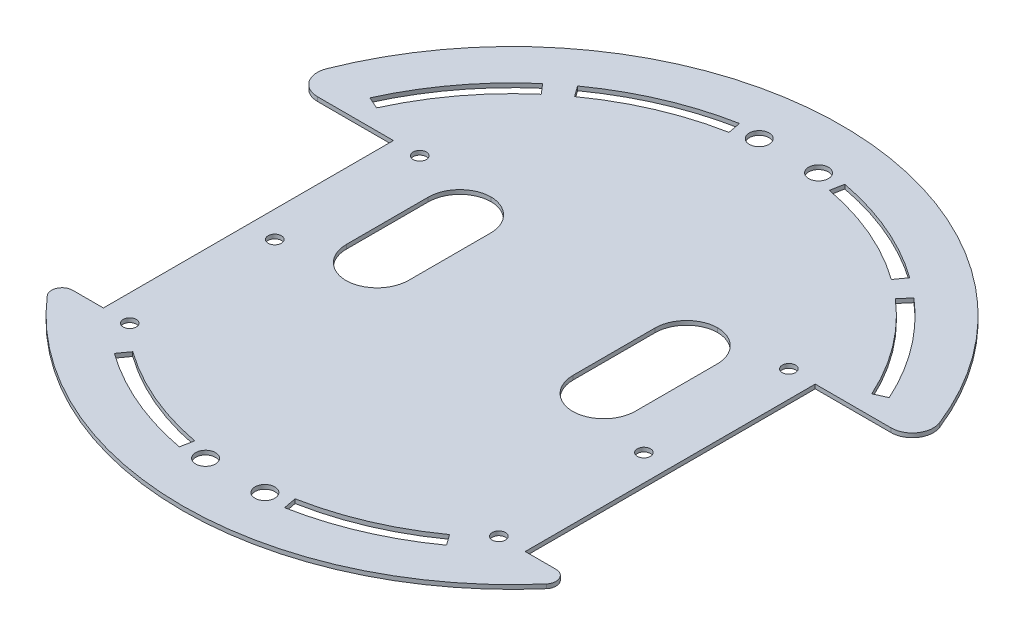
SolidWorks part; units mm, degrees
ref_plane "Front Plane" through (0, 0, 0) normal (0, 0, 1) x (1, 0, 0)
ref_plane "Top Plane" through (0, 0, 0) normal (0, 1, 0) x (1, 0, 0)
ref_plane "Right Plane" through (0, 0, 0) normal (1, 0, 0) x (0, 0, -1)
sketch "Sketch1" plane through (0, 0, 0) normal (0, 1, 0) x (1, 0, 0)
  line L0 (0, 0) -> (0, -79.375)
  line L1 (7.1438, -66.675) -> (-7.1437, -66.675)
  line L2 (50.8, 22.225) -> (76.2, 22.225)
  line L3 (-63.5, -47.625) -> (-50.8, -47.625)
  line L4 (-50.8, -47.625) -> (-50.8, 22.225)
  line L5 (63.5, -47.625) -> (50.8, -47.625)
  line L6 (50.8, -47.625) -> (50.8, 22.225)
  line L7 (-50.8, 22.225) -> (-76.2, 22.225)
  line L8 (0, 0) -> (-27.2811, 0)
  circle A0 centre (0, 0) radius 79.375
  circle A1 centre (-7.1437, -66.675) radius 1.5875
  circle A2 centre (7.1438, -66.675) radius 1.5875
  circle A3 centre (7.1438, 66.675) radius 1.5875
  circle A4 centre (-7.1437, 66.675) radius 1.5875
  point P7 (0, -66.675)
  dimension "D1" = 7.1437
  dimension "D3" = 50.8
  dimension "D6" = 3.175
  dimension "D2" = 12.7
  dimension "D4" = 69.85
  dimension "D5" = 47.625
extrude "Boss-Extrude5" add sketch "Sketch1" along normal blind 1.5875 contours A2 A0 L5 L6 L2 L7 L4 L3 A1 A3 region at (0, 0, -2.0947)
fillet "Fillet2" radius 2.54 1 edges at (-63.5, 0.7937, 47.625)
fillet "Fillet3" radius 2.54 1 edges at (63.5, 0.7937, 47.625)
fillet "Fillet4" radius 5.08 2 edges at (-76.2, 0.7937, -22.225) (76.2, 0.7937, -22.225)
sketch "Sketch2" plane through (0, 1.5875, 0) normal (0, 1, 0) x (1, 0, 0)
  line L0 (0, 0) -> (0, 79.375)
  line L1 (0, 0) -> (-67.0566, 0)
  line L2 (0, 0) -> (-61.0886, 27.6545)
  line L3 (0, 0) -> (-43.6778, 50.8806)
  line L4 (0, 0) -> (-63.2664, 22.225)
  line L5 (-50.8, 22.225) -> (-69.0955, 22.225) construction
  line L6 (0, 0) -> (0, 2.6153)
  line L7 (0, 0) -> (-39.0771, 54.4938)
  line L8 (0, 0) -> (-12.3858, 65.9028)
  line L9 (-62.5348, 28.3092) -> (-59.6424, 26.9998)
  line L10 (-43.6778, 50.8806) -> (-44.7118, 52.0852)
  line L11 (-43.6778, 50.8806) -> (-42.6438, 49.6761)
  line L12 (-39.0771, 54.4938) -> (-40.0022, 55.7839)
  line L13 (-39.0771, 54.4938) -> (-38.152, 53.2037)
  line L14 (-43.6778, 50.8806) -> (-42.6438, 49.6761)
  line L15 (-12.3858, 65.9028) -> (-12.0926, 64.3426)
  line L16 (-12.3858, 65.9028) -> (-12.679, 67.463)
  line L17 (61.5813, 22.225) -> (64.9466, 22.225)
  line L18 (50.8, 22.225) -> (69.0955, 22.225) construction
  line L19 (12.3858, 65.9028) -> (12.679, 67.463)
  line L20 (12.3858, 65.9028) -> (12.0926, 64.3426)
  line L21 (39.0771, 54.4938) -> (38.152, 53.2037)
  line L22 (43.6778, 50.8806) -> (42.6438, 49.6761)
  line L23 (39.0771, 54.4938) -> (40.0022, 55.7839)
  line L24 (43.6778, 50.8806) -> (42.6438, 49.6761)
  line L25 (43.6778, 50.8806) -> (44.7118, 52.0852)
  line L26 (62.5348, 28.3092) -> (59.6424, 26.9998)
  line L27 (-50.8, -41.2985) -> (-50.8, -43.7716)
  line L28 (-50.8, -47.625) -> (-50.8, 22.225) construction
  line L29 (50.8, -41.2985) -> (50.8, -46.1668)
  line L30 (50.8, -47.625) -> (50.8, 22.225) construction
  line L31 (39.0771, -54.4938) -> (40.0022, -55.7839)
  line L32 (39.0771, -54.4938) -> (38.152, -53.2037)
  line L33 (12.3858, -65.9028) -> (12.0926, -64.3426)
  line L34 (12.3858, -65.9028) -> (12.679, -67.463)
  line L35 (-12.3858, -65.9028) -> (-12.679, -67.463)
  line L36 (-12.3858, -65.9028) -> (-12.0926, -64.3426)
  line L37 (-39.0771, -54.4938) -> (-38.152, -53.2037)
  line L38 (-39.0771, -54.4938) -> (-40.0022, -55.7839)
  arc A0 (-63.2664, 22.225) -> (-50.8, -43.7716) centre (0, 0) ccw
  arc A1 (73.8199, 29.172) -> (-73.8199, 29.172) centre (0, 0) ccw construction
  circle A2 centre (-7.1437, 66.675) radius 2.3813
  circle A3 centre (7.1437, 66.675) radius 2.3813
  circle A4 centre (7.1437, -66.675) radius 2.3813
  circle A5 centre (-7.1437, -66.675) radius 2.3813
  arc A6 (12.679, -67.463) -> (40.0022, -55.7839) centre (0, 0) ccw
  arc A7 (-61.7686, 21.6988) -> (-50.8, -41.2985) centre (0, 0) ccw
  arc A8 (-44.7118, 52.0852) -> (-62.5348, 28.3092) centre (0, 0) ccw
  arc A9 (-42.6438, 49.6761) -> (-59.6424, 26.9998) centre (0, 0) ccw
  arc A10 (12.0926, 64.3426) -> (38.152, 53.2037) centre (0, 0) cw
  arc A11 (12.679, 67.463) -> (40.0022, 55.7839) centre (0, 0) cw
  arc A12 (42.6438, 49.6761) -> (59.6424, 26.9998) centre (0, 0) cw
  arc A13 (-12.679, 67.463) -> (-40.0022, 55.7839) centre (0, 0) ccw
  arc A14 (44.7118, 52.0852) -> (62.5348, 28.3092) centre (0, 0) cw
  arc A15 (-12.0926, 64.3426) -> (-38.152, 53.2037) centre (0, 0) ccw
  arc A16 (12.0926, -64.3426) -> (38.152, -53.2037) centre (0, 0) ccw
  arc A17 (-12.0926, -64.3426) -> (-38.152, -53.2037) centre (0, 0) cw
  arc A18 (50.8, -46.1668) -> (64.9466, 22.225) centre (0, 0) ccw
  arc A19 (50.8, -43.7716) -> (63.2664, 22.225) centre (0, 0) ccw
  arc A20 (50.8, -41.2985) -> (61.5813, 22.225) centre (0, 0) ccw
  arc A21 (-12.679, -67.463) -> (-40.0022, -55.7839) centre (0, 0) cw
  circle M13 centre (-7.1437, -66.675) radius 1.5875
  circle M14 centre (7.1438, -66.675) radius 1.5875
  circle M15 centre (7.1438, 66.675) radius 1.5875
  circle M16 centre (-7.1437, 66.675) radius 1.5875
  dimension "D2" = 4.7625
  dimension "D7" = 1.5875
  dimension "D8" = 3.175
  dimension "D1" = 5
  dimension "D3" = 25
  dimension "D4" = 5
  dimension "D5" = 25
extrude "Cut-Extrude1" cut sketch "Sketch2" against normal blind 2.54 contours A9 L3 L10 A8 L9 L2 | A15 L8 L16 A13 L12 L7 | A2 M16 | A3 M15 | A11 L19 L20 A10 L21 L23 | A14 L25 L22 A12 L26 | A21 L35 L36 A17 L37 L38 | A5 M13 | A4 M14 | A16 L33 L34 A6 L31 L32 region at (-53.2404, 1.5875, -39.9101) region at (-26.1525, 1.5875, -61.1833) region at (26.1525, 1.5875, -61.1833) region at (53.2404, 1.5875, -39.9101) region at (26.1525, 1.5875, 61.1833) region at (-26.1525, 1.5875, 61.1833) region at (-9.4576, 1.5875, -66.675) region at (4.8299, 1.5875, -66.675) region at (4.8299, 1.5875, 66.675) region at (-9.4576, 1.5875, 66.675)
sketch "Sketch3" plane through (0, 1.5875, 0) normal (0, 1, 0) x (1, 0, 0)
  line L0 (-50.8, 22.225) -> (-50.8, -47.625)
  line L1 (-50.8, -47.625) -> (-44.45, -47.625)
  line L2 (-50.8, 22.225) -> (-44.45, 22.225)
  line L3 (0, 0) -> (0, 32.9013)
  circle A0 centre (-44.45, -47.625) radius 1.5875
  circle A1 centre (-44.45, 22.225) radius 1.5875
  circle A2 centre (44.45, 22.225) radius 1.5875
  circle A3 centre (44.45, -47.625) radius 1.5875
  dimension "D2" = 3.175
  dimension "D4" = 3.175
  dimension "D1" = 6.35
  dimension "D3" = 6.35
extrude "Cut-Extrude2" cut sketch "Sketch3" against normal blind 2.54 contours A1 | A2 | A0 | A3 region at (-44.45, 1.5875, 46.0824) region at (-44.45, 1.5875, -23.7676) region at (44.45, 1.5875, -22.225) region at (44.45, 1.5875, 47.625)
sketch "Sketch4" plane through (0, 1.5875, 0) normal (0, 1, 0) x (1, 0, 0)
  line L0 (-44.45, -47.625) -> (-44.45, 22.225)
  line L1 (-44.45, 22.225) -> (-50.8, 22.225)
  line L2 (-50.8, -47.625) -> (-50.8, 22.225) construction
  line L3 (0, 0) -> (0, -67.5878)
  line L4 (44.45, -47.625) -> (44.45, 22.225)
  circle A0 centre (-44.45, 22.225) radius 1.5875
  circle A1 centre (-44.45, -12.7) radius 1.5875
  circle A2 centre (44.45, -12.7) radius 1.5875
  dimension "D2" = 3.175
  dimension "D1" = 69.85
extrude "Cut-Extrude3" cut sketch "Sketch4" against normal blind 2.54 contours L0 A1 | L0 A1 | A2 L4 | A2 L4 region at (-45.1238, 1.5875, 12.7) region at (-43.7762, 1.5875, 12.7) region at (43.7762, 1.5875, 12.7) region at (45.1238, 1.5875, 12.7)
sketch "Sketch5" plane through (0, 1.5875, 0) normal (0, 1, 0) x (1, 0, 0)
  line L0 (-50.8, -12.7) -> (-34.8, -12.7)
  line L1 (-50.8, -47.625) -> (-50.8, 22.225) construction
  line L2 (-50.8, 22.225) -> (-34.8, 22.225)
  line L3 (-34.8, 22.225) -> (-34.8, -12.7)
  line L4 (0, 0) -> (0, 64.5379)
  line L5 (-34.8, 22.225) -> (-19.8, 22.225)
  line L6 (-19.8, 22.225) -> (-19.8, -12.7)
  line L7 (-19.8, -12.7) -> (-34.8, -12.7)
  line L8 (19.8, -12.7) -> (34.8, -12.7)
  line L9 (19.8, 22.225) -> (19.8, -12.7)
  line L10 (34.8, 22.225) -> (19.8, 22.225)
  line L11 (34.8, 22.225) -> (34.8, -12.7)
  dimension "D1" = 16
  dimension "D2" = 16
extrude "Cut-Extrude4" cut sketch "Sketch5" against normal through all contours L7 L6 L5 L3 | L11 L10 L9 L8 region at (-27.3, 1.5875, -4.7625) region at (27.3, 1.5875, -4.7625)
fillet "Fillet5" radius 7.62 4 edges at (-19.8, 0.7937, 12.7) (-34.8, 0.7937, 12.7) (-19.8, 0.7937, -22.225) (-34.8, 0.7937, -22.225)
fillet "Fillet6" radius 7.62 4 edges at (34.8, 0.7937, 12.7) (34.8, 0.7937, -22.225) (19.8, 0.7937, -22.225) (19.8, 0.7937, 12.7)
sketch "Sketch6" plane through (0, 0, 0) normal (0, -1, 0) x (-1, 0, 0)
  circle A0 centre (0, 0) radius 79.375
extrude "Cut-Extrude5" cut sketch "Sketch6" against normal blind 0.5875
